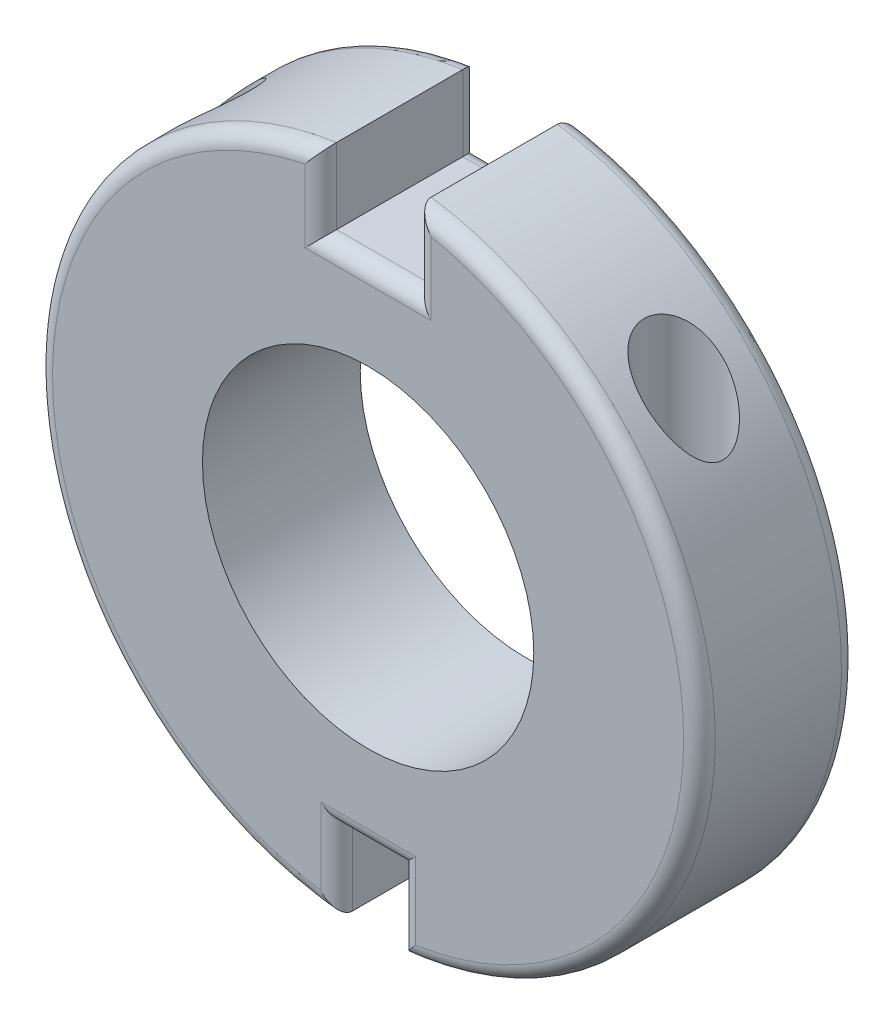
SolidWorks part; units mm, degrees
ref_plane "Plan de face" through (0, 0, 0) normal (0, 0, 1) x (1, 0, 0)
ref_plane "Plan de dessus" through (0, 0, 0) normal (0, 1, 0) x (1, 0, 0)
ref_plane "Plan de droite" through (0, 0, 0) normal (1, 0, 0) x (0, 0, -1)
sketch "Esquisse1" plane through (0, 0, 0) normal (0, 0, 1) x (1, 0, 0)
  line L0 (0, -21) -> (0, 21) construction
  line L1 (3, 16) -> (-3, 16)
  line L2 (-3, 16) -> (-3, 20.7846)
  line L3 (2, -15.9045) -> (-2, -15.9045)
  line L4 (-2, -15.9045) -> (-2, -20.9045)
  line L5 (-21, 0) -> (21, 0)
  line L6 (3, 16) -> (3, 20.7846)
  line L7 (2, -15.9045) -> (2, -20.9045)
  circle A0 centre (0, 0) radius 21
  circle A1 centre (0, 0) radius 10.5
  point P16 (0, 16)
  point P17 (0, -15.9045)
  dimension "D1" = 42
  dimension "D2" = 21
  dimension "D3" = 3
  dimension "D4" = 5
  dimension "D5" = 2
  dimension "D6" = 5
extrude "Boss.-Extru.1" add sketch "Esquisse1" along normal blind 10 contours A1 L0 L1 L2 A0 L5 | L0 A1 L5 A0 L6 L1 | L0 L3 L7 A0 L5 A1 | L3 L0 A1 L5 A0 L4 region at (-10.7795, -10.072, 0) region at (10.7795, -10.072, 0) region at (-10.9358, 9.9113, 0) region at (10.9358, 9.9113, 0)
sketch "Esquisse2" plane through (0, 0, 0) normal (0, 1, 0) x (1, 0, 0)
  line L0 (0, -10) -> (0, 0) construction
  line L1 (2, -10) -> (-2, -10) construction
  line L2 (-21, -5) -> (21, -5) construction
  line L3 (-21, 0) -> (-21, -10) construction
  line L4 (21, -10) -> (21, 0) construction
  circle A0 centre (15, -5) radius 1.25
  circle A1 centre (15, -5) radius 2.5
  circle A2 centre (-15, -5) radius 2.5
  circle A3 centre (-15, -5) radius 1.25
  dimension "D2" = 2.5
  dimension "D3" = 5
  dimension "D1" = 15
extrude "Enlèv. mat.-Extru.1" cut sketch "Esquisse2" against normal blind 10 and the other way blind 20 contours A0 | A3 region at (15, 0, 5) region at (-15, 0, 5)
extrude "Enlèv. mat.-Extru.2" cut sketch "Esquisse2<5>" along normal blind 10 from offset 7.5 contours A1 A0 | A2 | A3 region at (12.5707, 0, 5)
sketch "Esquisse2<5>" plane through (0, 0, 0) normal (0, 1, 0) x (1, 0, 0) same geometry as "Esquisse2"
fillet "Congé1" radius 1 16 edges at (-2, -18.4045, 0) (0, -15.9045, 0) (2, -18.4045, 0) (-20.994, -0.5036, 0) (-3, 18.3923, 0) (0, 16, 0) (3, 18.3923, 0) (20.994, -0.5036, 0) (-2, -18.4045, 10) (0, -15.9045, 10) (2, -18.4045, 10) (-3, 18.3923, 10) (0, 16, 10) (3, 18.3923, 10) (20.994, -0.5036, 10) (-20.994, -0.5036, 10)
